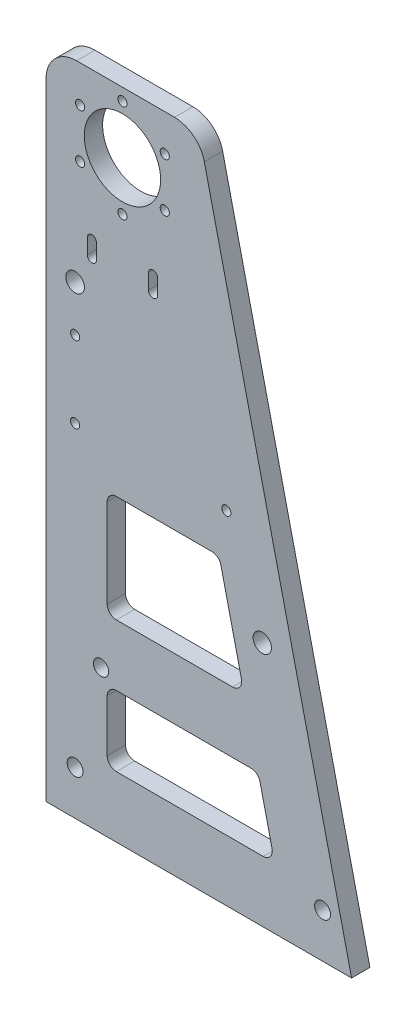
SolidWorks part; units mm, degrees
material "Policarbonato"
ref_plane "Plano frontal" through (0, 0, 0) normal (0, 0, 1) x (1, 0, 0)
ref_plane "Plano superior" through (0, 0, 0) normal (0, 1, 0) x (1, 0, 0)
ref_plane "Plano direito" through (0, 0, 0) normal (1, 0, 0) x (0, 0, -1)
sketch "Esboço1" plane through (0, 0, 0) normal (0, 0, 1) x (1, 0, 0)
  line L0 (0, 0) -> (0, 215)
  line L2 (100, 0) -> (0, 0)
  line L3 (0, 215) -> (50, 215)
  line L4 (50, 215) -> (100, 0)
  line L5 (10, 75.4302) -> (10, 15) construction
  line L6 (25, 215) -> (25, 175) construction
  line L7 (10, 15) -> (85.7122, 15) construction
  line L8 (85.7122, 15) -> (71.6586, 75.4302) construction
  line L9 (71.6586, 75.4302) -> (10, 75.4302) construction
  line L10 (20, 95) -> (20, 66)
  line L11 (23, 63) -> (61.0374, 63)
  line L12 (63.9594, 66.6795) -> (57.2152, 95.6795)
  line L13 (54.2932, 98) -> (23, 98)
  line L14 (20, 40) -> (20, 23)
  line L15 (23, 20) -> (71.0374, 20)
  line L16 (73.9594, 23.6795) -> (70.0059, 40.6795)
  line L17 (23, 43) -> (67.0839, 43)
  circle A0 centre (25, 195) radius 12.5
  circle A1 centre (25, 195) radius 16 construction
  circle A2 centre (25, 211) radius 1.5
  arc A8 (70.0059, 40.6795) -> (67.0839, 43) centre (67.0839, 40) ccw
  arc A9 (71.0374, 20) -> (73.9594, 23.6795) centre (71.0374, 23) ccw
  arc A10 (20, 23) -> (23, 20) centre (23, 23) ccw
  arc A11 (20, 40) -> (23, 43) centre (23, 40) cw
  arc A12 (57.2152, 95.6795) -> (54.2932, 98) centre (54.2932, 95) ccw
  arc A13 (61.0374, 63) -> (63.9594, 66.6795) centre (61.0374, 66) ccw
  arc A14 (20, 66) -> (23, 63) centre (23, 66) ccw
  arc A15 (20, 95) -> (23, 98) centre (23, 95) cw
  circle A16 centre (38.8564, 203) radius 1.5
  circle A17 centre (38.8564, 187) radius 1.5
  circle A18 centre (25, 179) radius 1.5
  circle A19 centre (11.1436, 187) radius 1.5
  circle A20 centre (11.1436, 203) radius 1.5
  circle A21 centre (18, 47) radius 2.5
  point P26 (22.5, 105)
  point P49 (20, 63)
  point P55 (25, 175)
  point P56 (25, 195)
  dimension "D3" = 20
  dimension "D4" = 25
  dimension "D6" = 32
  dimension "D7" = 3
  dimension "D21" = 3
  dimension "D15" = 18
  dimension "D16" = 47
  dimension "D17" = 5
  dimension "D1" = 215
  dimension "D2" = 100
  dimension "D5" = 50
  dimension "D9" = 25
  dimension "D10" = 6
  dimension "D11" = 20
  dimension "D12" = 20
  dimension "D13" = 15
  dimension "D14" = 20
  dimension "D18" = 10
  dimension "D20" = 20
  dimension "D22" = 23
  dimension "D8" = 35
extrude "Ressalto-extrusão2" add sketch "Esboço1" along normal blind 6
fillet "Filete1" radius 10 2 edges at (0, 215, 3) (50, 215, 3)
sketch "Esboço2" plane through (0, 0, 6) normal (0, 0, 1) x (1, 0, 0)
  line L0 (0, 0) -> (100, 0) construction
  line L1 (0, 205) -> (0, 0) construction
  line L2 (15, 164.21) -> (35, 164.21) construction
  line L3 (15, 161.71) -> (15, 166.71) construction
  line L4 (13.5, 161.71) -> (13.5, 166.71)
  line L5 (16.5, 161.71) -> (16.5, 166.71)
  line L6 (35, 161.71) -> (35, 166.71) construction
  line L7 (33.5, 161.71) -> (33.5, 166.71)
  line L8 (36.5, 161.71) -> (36.5, 166.71)
  circle A0 centre (9.5, 137) radius 1.5
  circle A1 centre (90.5, 14.5) radius 2.6
  circle A2 centre (9.5, 112) radius 1.5
  circle A3 centre (9.5, 152) radius 3.05
  circle A4 centre (15, 164.21) radius 1.5 construction
  circle A5 centre (35, 164.21) radius 1.5 construction
  arc A6 (13.5, 161.71) -> (16.5, 161.71) centre (15, 161.71) ccw
  arc A7 (16.5, 166.71) -> (13.5, 166.71) centre (15, 166.71) ccw
  arc A8 (33.5, 161.71) -> (36.5, 161.71) centre (35, 161.71) ccw
  arc A9 (36.5, 166.71) -> (33.5, 166.71) centre (35, 166.71) ccw
  circle A10 centre (59, 112) radius 1.5
  circle A11 centre (9.5, 14.5) radius 2.6
  point P2 (9.5, 112)
  point P3 (9.5, 137)
  point P18 (25, 195)
  point P20 (25, 164.21)
  point P22 (15, 164.21)
  point P30 (35, 164.21)
  dimension "D4" = 3
  dimension "D7" = 5.2
  dimension "D8" = 6.1
  dimension "D10" = 3
  dimension "D14" = 49.5
  dimension "D15" = 9.5
  dimension "D1" = 112
  dimension "D2" = 25
  dimension "D3" = 9.5
  dimension "D5" = 14.5
  dimension "D6" = 9.5
  dimension "D9" = 15
  dimension "D11" = 20
  dimension "D12" = 30.79
  dimension "D13" = 5
extrude "Corte-extrusão1" cut sketch "Esboço2" against normal through all
sketch "Esboço3" plane through (0, 0, 6) normal (0, 0, 1) x (1, 0, 0)
  circle A1 centre (70.7598, 80.3986) radius 3
extrude "Corte-extrusão2" cut sketch "Esboço3" against normal through all
